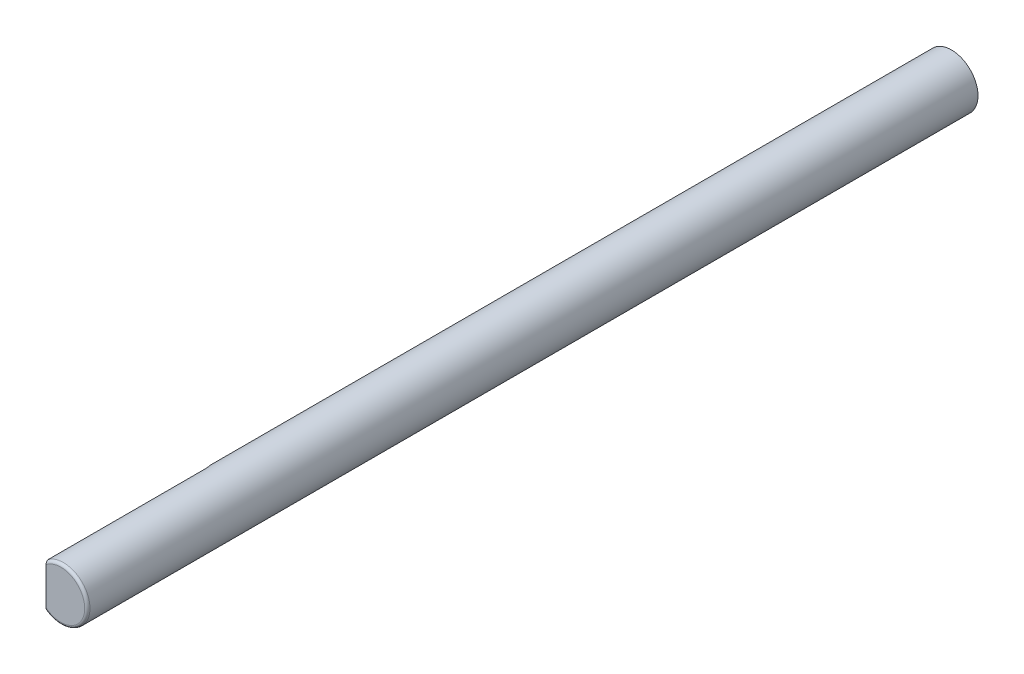
SolidWorks part; units mm, degrees
material "Acero aleado"
ref_plane "Plane1" through (0, 0, 0) normal (0, 0, 1) x (1, 0, 0)
ref_plane "Plane2" through (0, 0, 0) normal (0, 1, 0) x (1, 0, 0)
ref_plane "Plane3" through (0, 0, 0) normal (1, 0, 0) x (0, 0, -1)
sketch "Sketch1" plane through (0, 0, 0) normal (0, 0, 1) x (1, 0, 0)
  circle A0 centre (0, 0) radius 2.5
  dimension "D1" = 5
extrude "Extrude1" add sketch "Sketch1" along normal blind 84
fillet "Fillet1" radius 0.25 1 edges at (2.5, 0, 84)
sketch "Sketch2" plane through (0, 0, 0) normal (0, 1, 0) x (1, 0, 0)
  line L0 (-1.4, -84) -> (-1.4, -69)
  line L1 (-2.25, -84) -> (2.25, -84) construction
  line L2 (2.5, -83.75) -> (2.5, 0) construction
  line L3 (-1.4, -84) -> (-2.6966, -84)
  line L4 (-2.6966, -84) -> (-2.6966, -68.045)
  arc A0 (-1.4, -69) -> (-2.6966, -68.045) centre (-2.4, -69) ccw
  dimension "D3" = 2
  dimension "D1" = 3.9
  dimension "D2" = 15
extrude "Cut-Extrude1" cut sketch "Sketch2" against normal blind 3 and the other way blind 3
